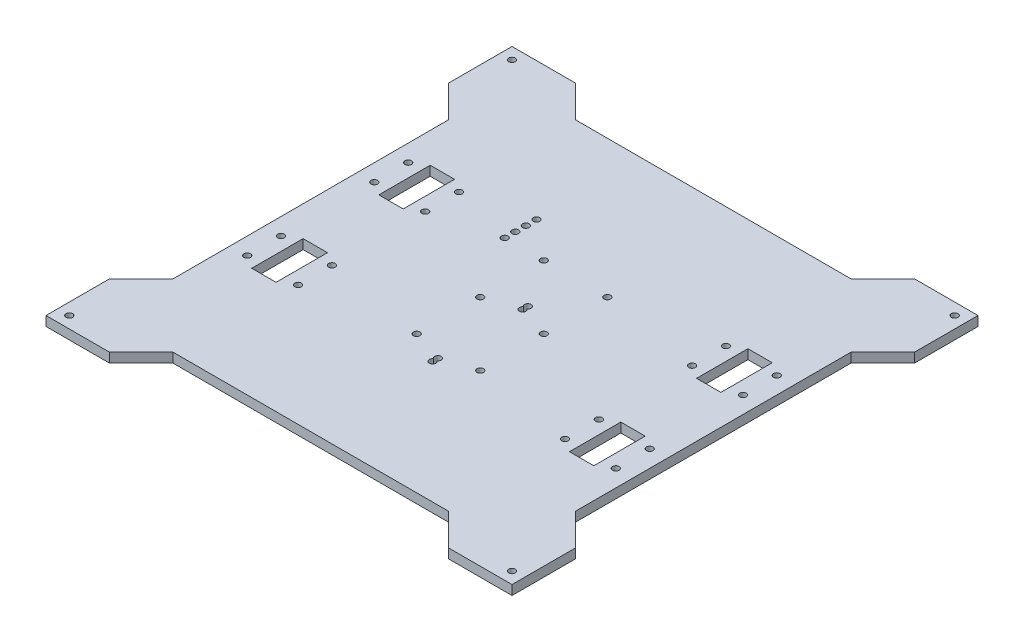
SolidWorks part; units mm, degrees
ref_plane "Front Plane" through (0, 0, 0) normal (0, 0, 1) x (1, 0, 0)
ref_plane "Top Plane" through (0, 0, 0) normal (0, 1, 0) x (1, 0, 0)
ref_plane "Right Plane" through (0, 0, 0) normal (1, 0, 0) x (0, 0, -1)
sketch "Sketch1" plane through (0, 0, 0) normal (0, 1, 0) x (1, 0, 0)
  line L1 (-110, 110) -> (110, 110)
  line L2 (-110, 110) -> (-110, -110)
  line L3 (-110, -110) -> (110, -110)
  line L4 (110, 110) -> (110, -110)
  line L5 (-110, 110) -> (110, -110) construction
  line L6 (-110, -110) -> (110, 110) construction
  point P0 (0, 0)
  dimension "D1" = 220
  dimension "D2" = 220
extrude "Square" add sketch "Sketch1" along normal blind 4.5
sketch "Sketch2" plane through (0, 4.5, 0) normal (0, 1, 0) x (1, 0, 0)
  line L0 (0, 110) -> (0, -110) construction
  line L1 (110, 110) -> (-110, 110) construction
  line L2 (-110, -110) -> (110, -110) construction
  line L3 (-110, 0) -> (110, 0) construction
  line L4 (-110, 110) -> (-110, -110) construction
  line L5 (110, -110) -> (110, 110) construction
  line L6 (75, 110) -> (75, -110) construction
  line L7 (75, 30) -> (0, 30) construction
  line L8 (75, -30) -> (0, -30) construction
  circle A0 centre (87, 38) radius 1.55
  circle A1 centre (87, 22) radius 1.55
  circle A2 centre (63, 22) radius 1.55
  circle A3 centre (63, 38) radius 1.55
  circle A4 centre (-63, 38) radius 1.55
  circle A5 centre (-63, 22) radius 1.55
  circle A6 centre (-87, 22) radius 1.55
  circle A7 centre (-87, 38) radius 1.55
  circle A8 centre (-87, 22) radius 1.55
  circle A9 centre (-87, 38) radius 1.55
  circle A10 centre (-63, 38) radius 1.55
  circle A11 centre (-63, 22) radius 1.55
  circle A12 centre (63, 22) radius 1.55
  circle A13 centre (63, 38) radius 1.55
  circle A14 centre (87, 38) radius 1.55
  circle A15 centre (87, 22) radius 1.55
  circle A16 centre (87, -22) radius 1.55
  circle A17 centre (87, -38) radius 1.55
  circle A18 centre (63, -38) radius 1.55
  circle A19 centre (63, -22) radius 1.55
  circle A20 centre (-63, -22) radius 1.55
  circle A21 centre (-63, -38) radius 1.55
  circle A22 centre (-87, -38) radius 1.55
  circle A23 centre (-87, -22) radius 1.55
  circle A24 centre (-87, -38) radius 1.55
  circle A25 centre (-87, -22) radius 1.55
  circle A26 centre (-63, -22) radius 1.55
  circle A27 centre (-63, -38) radius 1.55
  circle A28 centre (63, -38) radius 1.55
  circle A29 centre (63, -22) radius 1.55
  circle A30 centre (87, -22) radius 1.55
  circle A31 centre (87, -38) radius 1.55
  dimension "D6" = 3.1
  dimension "D7" = 3.1
  dimension "D1" = 75
  dimension "D2" = 30
  dimension "D3" = 16
  dimension "D5" = 12
extrude "LM8UU-Holders" cut sketch "Sketch2" against normal through all contours A7 | A6 | A5 | A4 | A20 | A21 | A22 | A23 | A19 | A18 | A17 | A16 | A1 | A0 | A3 | A2 region at (87, 4.5, -38) region at (87, 4.5, -22) region at (63, 4.5, -22) region at (63, 4.5, -38) region at (-63, 4.5, -38) region at (-63, 4.5, -22) region at (-87, 4.5, -22) region at (-87, 4.5, -38) region at (87, 4.5, 22) region at (87, 4.5, 38) region at (63, 4.5, 38) region at (63, 4.5, 22) region at (-63, 4.5, 22) region at (-63, 4.5, 38) region at (-87, 4.5, 38) region at (-87, 4.5, 22)
sketch "Sketch3" plane through (0, 4.5, 0) normal (0, 1, 0) x (1, 0, 0)
  line L0 (0, -110) -> (0, 110) construction
  line L1 (-110, -110) -> (110, -110) construction
  line L2 (110, 110) -> (-110, 110) construction
  line L3 (110, -15) -> (-110, -15) construction
  line L6 (15, -30) -> (-15, -30) construction
  line L7 (15, 0) -> (-15, 0) construction
  line L8 (110, -110) -> (110, 110) construction
  line L9 (-110, 110) -> (-110, -110) construction
  line L10 (110, 0) -> (-110, 0) construction
  circle A0 centre (-15, -30) radius 1.55
  circle A1 centre (15, -30) radius 1.55
  circle A2 centre (15, 0) radius 1.55
  circle A3 centre (-15, 0) radius 1.55
  point P16 (0, -30)
  dimension "D1" = 3.1
  dimension "D2" = 15
  dimension "D3" = 15
  dimension "D5" = 15
extrude "DefaultBelt" cut sketch "Sketch3" against normal through all
sketch "Sketch4" plane through (0, 4.5, 0) normal (0, 1, 0) x (1, 0, 0)
  line L0 (0, 110) -> (0, -110) construction
  line L1 (110, 110) -> (-110, 110) construction
  line L2 (-110, -110) -> (110, -110) construction
  line L3 (-15, -1.55) -> (-15, -28.45) construction
  line L4 (15, -28.45) -> (15, -1.55) construction
  line L5 (15, -15) -> (-15, -15) construction
  arc A0 (-0.9165, 6.25) -> (0.9165, 6.25) centre (0, 5) ccw
  arc A1 (0.9165, 6.25) -> (-0.9165, 6.25) centre (0, 7.5) ccw
  arc A2 (0.9165, -36.25) -> (-0.9165, -36.25) centre (0, -37.5) cw
  arc A3 (-0.9165, -36.25) -> (0.9165, -36.25) centre (0, -35) cw
  circle A4 centre (-15, 0) radius 1.55 construction
  circle A5 centre (-15, -30) radius 1.55 construction
  circle A6 centre (15, -30) radius 1.55 construction
  circle A7 centre (15, 0) radius 1.55 construction
  dimension "D1" = 3.1
  dimension "D2" = 3.1
  dimension "D3" = 20
  dimension "D4" = 22.5
extrude "BeltOptions" cut sketch "Sketch4" against normal through all
sketch "Sketch5" plane through (0, 4.5, 0) normal (0, 1, 0) x (1, 0, 0)
  line L0 (-110, 0) -> (110, 0) construction
  line L1 (-110, 110) -> (-110, -110) construction
  line L2 (110, -110) -> (110, 110) construction
  line L3 (0, 110) -> (0, -110) construction
  line L4 (110, 110) -> (-110, 110) construction
  line L5 (-110, 110) -> (-110, 80)
  line L6 (-110, 80) -> (-95, 65)
  line L7 (-95, 65) -> (-95, -65)
  line L8 (0, 0) -> (-110, 110) construction
  line L9 (-65, 95) -> (65, 95)
  line L10 (-80, 110) -> (-65, 95)
  line L11 (-110, 110) -> (-80, 110)
  line L12 (-95, 65) -> (-95, -65)
  line L13 (0, 0) -> (110, 110) construction
  line L14 (95, 65) -> (95, -65)
  line L15 (110, 110) -> (80, 110)
  line L16 (80, 110) -> (65, 95)
  line L17 (95, 65) -> (95, -65)
  line L18 (110, 80) -> (95, 65)
  line L19 (110, 110) -> (110, 80)
  line L20 (0, 0) -> (110, -110) construction
  line L21 (0, 0) -> (-110, -110) construction
  line L22 (110, -110) -> (110, -80)
  line L23 (110, -80) -> (95, -65)
  line L24 (80, -110) -> (65, -95)
  line L25 (110, -110) -> (80, -110)
  line L26 (-110, -110) -> (-80, -110)
  line L27 (-80, -110) -> (-65, -95)
  line L28 (-65, -95) -> (65, -95)
  line L29 (-110, -80) -> (-95, -65)
  line L30 (-110, -110) -> (-110, -80)
  point P24 (0, 95)
  point P32 (95, 0)
  point P35 (-95, 0)
  point P36 (0, -95)
  circle M16 centre (15, -30) radius 1.55
  circle M18 centre (63, 38) radius 1.55
  circle M20 centre (87, 22) radius 1.55
  circle M22 centre (87, -38) radius 1.55
  circle M23 centre (63, -38) radius 1.55
  circle M24 centre (63, -22) radius 1.55
  circle M25 centre (-87, -22) radius 1.55
  circle M26 centre (-87, -38) radius 1.55
  circle M27 centre (-63, -38) radius 1.55
  circle M28 centre (-63, -22) radius 1.55
  circle M29 centre (-63, 38) radius 1.55
  circle M30 centre (-63, 22) radius 1.55
  circle M31 centre (-87, 22) radius 1.55
  circle M32 centre (-87, 38) radius 1.55
  line M33 (110, -110) -> (110, 110)
  line M34 (110, 110) -> (-110, 110)
  line M35 (-110, 110) -> (-110, -110)
  line M36 (-110, -110) -> (110, -110)
  dimension "D1" = 15
  dimension "D2" = 30
  dimension "D3" = 45
  dimension "D4" = 45
extrude "Shaping" cut sketch "Sketch5" against normal blind 10 flip side to cut contours L29 L27 L28 L24 L23 L14 L18 L16 L9 L10 L6 L7 M35 M36 M33 M34 M16 M18 M20 M22 M24 M26 M28 M30 M32 M31 M29 M27 M25 M23 region at (0.0423, 4.5, -0.013)
sketch "Sketch6" plane through (0, 4.5, 0) normal (0, 1, 0) x (1, 0, 0)
  line L0 (-110, 110) -> (110, -110) construction
  line L1 (-110, -110) -> (110, 110) construction
  line L2 (110, 80) -> (110, 110) construction
  line L3 (0, 95) -> (0, -95) construction
  line L4 (-65, 95) -> (65, 95) construction
  line L5 (-65, -95) -> (65, -95) construction
  line L6 (-95, 0) -> (95, 0) construction
  line L7 (-95, 65) -> (-95, -65) construction
  line L8 (95, 65) -> (95, -65) construction
  circle A0 centre (-104.5, 104.5) radius 1.55
  circle A1 centre (104.5, 104.5) radius 1.55
  circle A2 centre (104.5, -104.5) radius 1.55
  circle A3 centre (-104.5, -104.5) radius 1.55
  dimension "D2" = 3.1
  dimension "D1" = 45
  dimension "D3" = 104.5
extrude "Cut-Extrude5" cut sketch "Sketch6" against normal through all
sketch "Sketch7" plane through (0, 4.5, 0) normal (0, 1, 0) x (1, 0, 0)
  line L0 (-87, 38) -> (-63, 22) construction
  line L1 (-63, 22) -> (-87, 22) construction
  line L2 (-87, 22) -> (-63, 38) construction
  line L3 (-63, 38) -> (-87, 38) construction
  line L4 (-95, 0) -> (95, 0) construction
  line L5 (-80.75, 42.125) -> (-69.25, 42.125)
  line L6 (-80.75, 42.125) -> (-80.75, 17.875)
  line L7 (-80.75, 17.875) -> (-69.25, 17.875)
  line L8 (-69.25, 42.125) -> (-69.25, 17.875)
  line L9 (-80.75, 42.125) -> (-69.25, 17.875) construction
  line L10 (-80.75, 17.875) -> (-69.25, 42.125) construction
  line L11 (-95, 65) -> (-95, -65) construction
  line L12 (95, 65) -> (95, -65) construction
  line L13 (0, -95) -> (0, 95) construction
  line L14 (-65, -95) -> (65, -95) construction
  line L15 (-65, 95) -> (65, 95) construction
  line L16 (-80.75, -17.875) -> (-69.25, -42.125) construction
  line L17 (-80.75, -42.125) -> (-69.25, -17.875) construction
  line L18 (-63, -38) -> (-87, -38) construction
  line L19 (-87, -22) -> (-63, -38) construction
  line L20 (-63, -22) -> (-87, -22) construction
  line L21 (-87, -38) -> (-63, -22) construction
  line L22 (-69.25, -42.125) -> (-69.25, -17.875)
  line L23 (-80.75, -17.875) -> (-69.25, -17.875)
  line L24 (-80.75, -42.125) -> (-80.75, -17.875)
  line L25 (-80.75, -42.125) -> (-69.25, -42.125)
  line L26 (-80.75, 17.875) -> (-69.25, 42.125) construction
  line L27 (80.75, 17.875) -> (69.25, 42.125) construction
  line L28 (87, -38) -> (63, -22) construction
  line L29 (63, -22) -> (87, -22) construction
  line L30 (87, -22) -> (63, -38) construction
  line L31 (63, -38) -> (87, -38) construction
  line L32 (80.75, -42.125) -> (69.25, -17.875) construction
  line L33 (80.75, -17.875) -> (69.25, -42.125) construction
  line L34 (80.75, 17.875) -> (69.25, 42.125) construction
  line L35 (80.75, 42.125) -> (69.25, 17.875) construction
  line L36 (63, 38) -> (87, 38) construction
  line L37 (87, 22) -> (63, 38) construction
  line L38 (63, 22) -> (87, 22) construction
  line L39 (87, 38) -> (63, 22) construction
  line L40 (80.75, -42.125) -> (69.25, -42.125)
  line L41 (80.75, -42.125) -> (80.75, -17.875)
  line L42 (80.75, -17.875) -> (69.25, -17.875)
  line L43 (69.25, -42.125) -> (69.25, -17.875)
  line L44 (69.25, 42.125) -> (69.25, 17.875)
  line L45 (80.75, 17.875) -> (69.25, 17.875)
  line L46 (80.75, 42.125) -> (80.75, 17.875)
  line L47 (80.75, 42.125) -> (69.25, 42.125)
  point P4 (-75, 30)
  point P33 (-75, -30)
  point P50 (75, -30)
  point P51 (75, 30)
  dimension "D1" = 11.5
  dimension "D2" = 24.25
extrude "Cut-Extrude6" cut sketch "Sketch7" against normal through all
sketch "Sketch8" plane through (0, 4.5, 0) normal (0, 1, 0) x (1, 0, 0)
  line L3 (-65, 95) -> (65, 95) construction
  line L4 (-33.45, 45) -> (-33.45, 30) construction
  circle A0 centre (-33.45, 45) radius 1.55
  circle A1 centre (-33.45, 40) radius 1.55
  circle A2 centre (-33.45, 35) radius 1.55
  circle A3 centre (-33.45, 30) radius 1.55
  dimension "D1" = 3.1
  dimension "D2" = 50
extrude "EndstopTrigger" cut sketch "Sketch8" against normal through all
pattern_linear "LPattern1" count 2 spacing 30 along (0, 0, -1) of "DefaultBelt"
equation "\"X-ROD-SPACING\"=45"
equation "\"Y-ROD-SPACING\"=75"
equation "\"Z-ROD-SPACING\"=17.5"
equation "\"Y-BED-OFFSET\"=2"
equation "\"Y-BED-ROD-INSET\"=3.5"
equation "\"T-SLOT-NUT-FILLET-RADIUS\"=0.25"
equation "\"T-SLOT-SCREW-SHAFT-RADIUS\"=1.75"
equation "\"T-SLOT-SCREW-SHAFT-CUTOUT-LENGTH\"=10.5"
equation "\"T-SLOT-NUT-DEPTH\"=4.2"
equation "\"T-SLOT-NUT-WIDTH\"=3"
equation "\"T-SLOT-NUT-END-DISTANCE\"=8"
equation "\"ACRYLIC-THICKNESS\"=10"
equation "\"ACRYLIC-THICKNESS2\"=4.5"
equation "\"ACRYLIC-TAB-CUTOUT-SIZE\"=\"ACRYLIC-THICKNESS\"+\"ACRYLIC-TAB-TOLERANCE\"*2"
equation "\"ACRYLIC-TAB-WIDTH\"=\"ACRYLIC-THICKNESS\""
equation "\"ACRYLIC-M3-HOLE\"=3.1"
equation "\"SMOOTHROD-CAP-SCREW-DISTANCE\"=20"
equation "\"FRAME-WIDTH-INNER\"=370"
equation "\"NEMA17-HOLE-SPACING\"=31"
equation "\"NEMA17-CENTRAL-CUTOUT\"=22.5"
equation "\"Z-BRACKET-REACH\"=55"
equation "\"TOP-BRACKET-SPACING\"=40"
equation "\"SMOOTHROD-X-LENGTH\"=350"
equation "\"SMOOTHROD-Y-LENGTH\"=350"
equation "\"SMOOTHROD-Z-LENGTH\"=350"
equation "\"SMOOTHROD-TIGHTENING-HEADROOM\"=.25"
equation "\"LEADSCREW-Z-LENGTH\"=300"
equation "\"SCREW-LENGTH-FRAME\"=\"ACRYLIC-THICKNESS\" + 10"
equation "\"SCREW-HEAD-RADIUS\"=6"
equation "\"PRINTED-X-SMOOTHROD-DIAMETER\"=8.2"
equation "\"PRINTED-X-SMOOTHROD-CUTOUT\"=10"
equation "\"PRINTED-X-BASE-HEIGHT\"=10"
equation "\"PRINTED-LM8UU-CUTOUT-SIZE\"=15.25"
equation "\"PRINTED-LM8UU-CUTOUT-LENGTH\"=24.5"
equation "\"PRINTED-X-IDLER-HEIGHT\"=16"
equation "\"PSU-MOUNTING-WIDTH\"=95"
equation "\"PSU-MOUNTING-HEIGHT\"=177"
equation "\"Y-BELT-TO-ROD-DISTANCE\"=20"
equation "\"D6@Sketch2\"=\"ACRYLIC-M3-HOLE\""
equation "\"D7@Sketch2\"=\"ACRYLIC-M3-HOLE\""
equation "\"D1@Sketch2\"=\"Y-ROD-SPACING\""
equation "\"D1@Sketch3\"=\"ACRYLIC-M3-HOLE\""
equation "\"D2@Sketch6\"=\"ACRYLIC-M3-HOLE\""
equation "\"Y-BED-SCREW-SPACING\"=209"
equation "\"Y-BED-SCREW-CUTOUT-SLOT-HEIGHT\"=2"
equation "\"ACRYLIC-TAB-TOLERANCE\"=.1"
equation "\"Z-ROD-INSET\"=16"
equation "\"SCREW-LENGTH-MOTOR\"=\"ACRYLIC-THICKNESS\" + 5"
equation "\"SCREW-LENGTH-EXTRUDER\"=28"
equation "\"PRINTED-M3-HOLE\"=3.5"
equation "\"SPOOL-HOLDER-ROD-SPACING\"=150"
equation "\"ACRYLIC-X-CARRIAGE-WIDTH\"=55"
equation "\"ACRYLIC-X-CARRIAGE-HEIGHT\"=75"
equation "\"ACRYLIC-X-CARRIAGE-LM8UU-CUTOUT-WIDTH\"=24.25"
equation "\"ACRYLIC-X-CARRIAGE-LM8UU-CUTOUT-HEIGHT\"=11.5"
equation "\"ACRYLIC-X-CARRIAGE-SCREW-SPACING-X\"=15"
equation "\"ACRYLIC-X-CARRIAGE-SCREW-SPACING-Y\"=33"
equation "\"ACRYLIC-X-CARRIAGE-CENTER-TAB-SPACING\"=14"
equation "\"ACRYLIC-X-CARRIAGE-EXTRUDER-OFFSET\"=26"
equation "\"ACRYLIC-X-CARRIAGE-EXTRUDER-ANGLE\"=90"
equation "\"ACRYLIC-X-CARRIAGE-EXTRUDER-SHELF-DEPTH\"=\"ACRYLIC-X-CARRIAGE-EXTRUDER-OFFSET\" + 28"
equation "\"ACRYLIC-X-CARRIAGE-EXTRUDER-BRACE-SPACING\"=23"
equation "\"ACRYLIC-X-CARRIAGE-EXTRUDER-BRACE-TAB-OFFSET\"=20"
equation "\"ACRYLIC-X-CARRIAGE-EXTRUDER-BRACE-HEIGHT\"=35"
equation "\"ACRYLIC-X-CARRIAGE-EXTRUDER-BRACE-SCREW-SPACING\"=22"
equation "\"ACRYLIC-X-CARRIAGE-DUAL-WIDTH-MULTIPLIER\"=1.65"
equation "\"ACRYLIC-X-CARRIAGE-DUAL-HOTEND-SPACING\"=42"
equation "\"ACRYLIC-X-CARRIAGE-DUAL-WIDTH\"=103"
equation "\"ACRYLIC-X-CARRIAGE-DUAL-HOTEND-SEPARATION\"=35"
equation "\"ACRYLIC-X-CARRIAGE-DUAL-MOUNT-PLATE-DEPTH\"=76"
equation "\"ACRYLIC-X-CARRIAGE-DUAL-MOUNT-BRACE-WIDTH\"=45"
equation "\"ACRYLIC-X-CARRIAGE-DUAL-MOUNT-SCREW-WIDTH\"=40"
equation "\"BLOWER-FAN-WIDTH\"=15"
equation "\"D1@Sketch7\"=\"ACRYLIC-X-CARRIAGE-LM8UU-CUTOUT-HEIGHT\""
equation "\"D2@Sketch7\"=\"ACRYLIC-X-CARRIAGE-LM8UU-CUTOUT-WIDTH\""
equation "\"D1@Sketch8\"=\"ACRYLIC-M3-HOLE\""
equation "\"D2@Sketch4\"=\"ACRYLIC-M3-HOLE\""
equation "\"D1@Sketch4\"=\"ACRYLIC-M3-HOLE\""
equation "\"D3@Sketch4\"=20"
